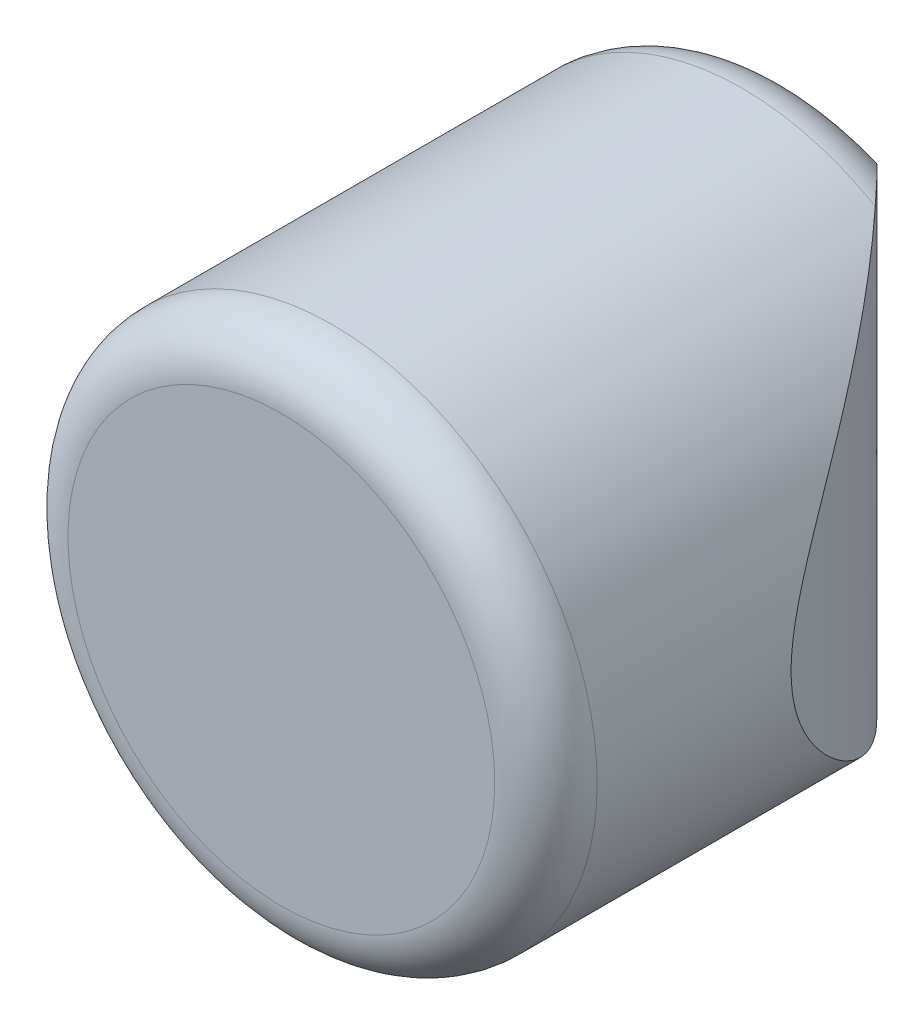
SolidWorks part; units mm, degrees
ref_plane "Front Plane" through (0, 0, 0) normal (0, 0, 1) x (1, 0, 0)
ref_plane "Top Plane" through (0, 0, 0) normal (0, 1, 0) x (1, 0, 0)
ref_plane "Right Plane" through (0, 0, 0) normal (1, 0, 0) x (0, 0, -1)
sketch "Sketch2" plane through (0, 0, 0) normal (0, 0, 1) x (1, 0, 0)
  circle A0 centre (0, 0) radius 15.5
  dimension "D1" = 31
extrude "Boss-Extrude1" add sketch "Sketch2" along normal blind 30
ref_point "Point1"
ref_point "Point2"
fillet "Fillet1" radius 3 2 edges at (15.5, 0, 30) (15.5, 0, 0)
sketch "Sketch3" plane through (0, 0, 0) normal (0, 1, 0) x (1, 0, 0)
  line L0 (-50, 0) -> (50, 0) construction
  line L1 (0, 0) -> (1000, 0) construction
  line L3 (4.8542, 0) -> (19.2064, 0)
  line L4 (19.2064, 0) -> (19.2064, -15.6367)
  line L5 (19.2064, -15.6367) -> (15.5, -15.6367)
  line L6 (12.5, 0) -> (-12.5, 0) construction
  spline S0 degree 2 poles (4.8542, 0) (12.0007, -6.6321) (15.5, -15.6367) knots 0 0 0 1 1 1
  point P3 (15.5, -27)
  point P4 (15.5, -16.159)
extrude "Cut-Extrude1" cut sketch "Sketch3" against normal blind 20 and the other way blind 20
